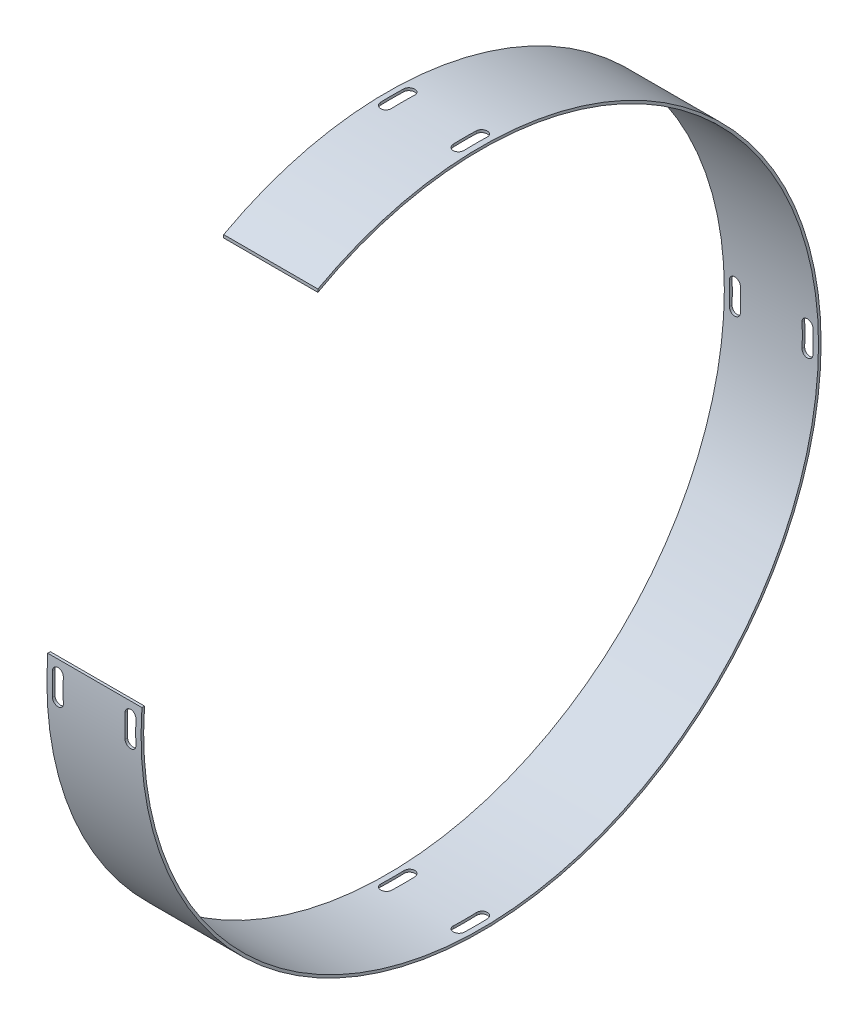
SolidWorks part; units mm, degrees
material "6061 Alloy"
ref_plane "Front Plane" through (0, 0, 0) normal (0, 0, 1) x (1, 0, 0)
ref_plane "Top Plane" through (0, 0, 0) normal (0, 1, 0) x (1, 0, 0)
ref_plane "Right Plane" through (0, 0, 0) normal (1, 0, 0) x (0, 0, -1)
sketch "Sketch1" plane through (0, 0, 0) normal (1, 0, 0) x (0, 0, -1)
  circle A0 centre (0, 0) radius 100
  circle A1 centre (0, 0) radius 99.238
  dimension "D1" = 200
  dimension "D2" = 0.762
extrude "Boss-Extrude1" add sketch "Sketch1" along normal blind 27.7
ref_plane "Plane1" through (0, 0, 100) normal (0, 0, 1) x (1, 0, 0)
hole_wizard "M3 Clearance Slot1" positions "Sketch2" profile "Sketch3" size "M3" standard "ANSI Metric" slot yes end condition through all
sketch "Sketch2" plane through (0, 0, 100) normal (0, 0, 1) x (1, 0, 0)
  line L0 (27.7, -100) -> (27.7, 100) construction
  line L1 (0, 100) -> (0, -100) construction
  line L2 (24.525, -5) -> (24.525, 5) construction
  point P0 (24.525, 0)
  point P2 (3.175, 0)
  point P12 (0, 0)
  point P13 (0, 0)
  point P15 (0, 0)
  dimension "D1" = 3.175
  dimension "D2" = 3.175
sketch "Sketch3" plane through (24.525, 0, 100) normal (1, 0, 0) x (0, -1, 0)
  line L0 (0, 0) -> (0, 200)
  line L1 (0, 200) -> (1.6, 200)
  line L2 (1.6, 200) -> (1.6, 0)
  line L5 (1.6, 0) -> (0, 0)
  line L11 (0, -6.35) -> (0, 107.95) construction
  dimension "Thru Hole Dia." = 3.2
  dimension "Thru Hole Depth" = 200
ref_plane "Plane2" through (0, 100, 0) normal (0, 1, 0) x (1, 0, 0)
hole_wizard "M3 Clearance Slot2" positions "Sketch4" profile "Sketch5" size "M3" standard "ANSI Metric" slot yes end condition through all
sketch "Sketch4" plane through (0, 100, 0) normal (0, 1, 0) x (1, 0, 0)
  line L0 (27.7, -100) -> (27.7, 100) construction
  line L1 (0, 100) -> (0, -100) construction
  line L2 (24.525, -5) -> (24.525, 5) construction
  point P0 (24.525, 0)
  point P2 (3.175, 0)
  point P12 (0, 0)
  point P14 (0, 0)
  point P19 (6.4505, -0.0968)
  point P20 (0, 0)
  dimension "D1" = 3.175
  dimension "D2" = 3.175
sketch "Sketch5" plane through (24.525, 100, 0) normal (1, 0, 0) x (0, 0, 1)
  line L0 (0, 0) -> (0, 200)
  line L1 (0, 200) -> (1.6, 200)
  line L2 (1.6, 200) -> (1.6, 0)
  line L5 (1.6, 0) -> (0, 0)
  line L11 (0, -6.35) -> (0, 107.95) construction
  dimension "Thru Hole Dia." = 3.2
  dimension "Thru Hole Depth" = 200
ref_plane "Plane3" through (0, 0, 0) normal (0, 0.7071, -0.7071) x (-1, 0, 0)
ref_plane "Plane4" through (0, 0, 0) normal (0, 0.7071, 0.7071) x (-1, 0, 0)
sketch "Sketch7" plane through (0, 0, 0) normal (0, 0.7071, 0.7071) x (-1, 0, 0)
  line L0 (-27.7, 7.5) -> (-27.7, -7.5) construction
  line L1 (-27.7, 7.5) -> (-21.35, 7.5) construction
  line L2 (-27.7, -7.5) -> (-21.35, -7.5) construction
  line L3 (-21.35, 7.5) -> (-21.35, -7.5) construction
  line L4 (-27.7, 100) -> (-27.7, -100) construction
  line L5 (-28.2, 8) -> (-20.85, 8)
  line L6 (-20.85, 8) -> (-20.85, -8)
  line L7 (-28.2, -8) -> (-20.85, -8)
  line L8 (-28.2, 8) -> (-28.2, -8)
  point P6 (-21.35, 0)
  dimension "D1" = 6.35
  dimension "D2" = 15
  dimension "D3" = 0.5
extrude "Cut-Extrude2" [suppressed] cut sketch "Sketch7" against normal through all both and the other way through all
sketch "Sketch8" plane through (0, 100, 0) normal (0, 1, 0) x (1, 0, 0)
  line L1 (27.85, -48) -> (20.85, -48) construction
  line L2 (27.85, -48) -> (27.85, -100) construction
  line L3 (27.85, -100) -> (20.85, -100) construction
  line L4 (20.85, -48) -> (20.85, -100) construction
  line L5 (4.775, -100) -> (22.925, -100) construction
  line L6 (27.85, -48) -> (-0.15, -48)
  line L7 (13.85, -1100) -> (13.85, 48900) construction
  line L8 (-0.15, -100) -> (6.85, -100) construction
  line L9 (6.85, -48) -> (6.85, -100) construction
  line L10 (-0.15, -48) -> (6.85, -48) construction
  line L11 (-0.15, -48) -> (-0.15, -100) construction
  line L12 (27.85, -48) -> (27.85, -100)
  line L13 (27.85, -100) -> (-0.15, -100)
  line L14 (-0.15, -48) -> (-0.15, -100)
  point P14 (13.85, -100)
  dimension "D1" = 7
  dimension "D2" = 52
  dimension "D3" = 7
extrude "Cut-Extrude3" cut sketch "Sketch8" against normal offset from surface (93 mm away) 7 up to plane "Top Plane"
